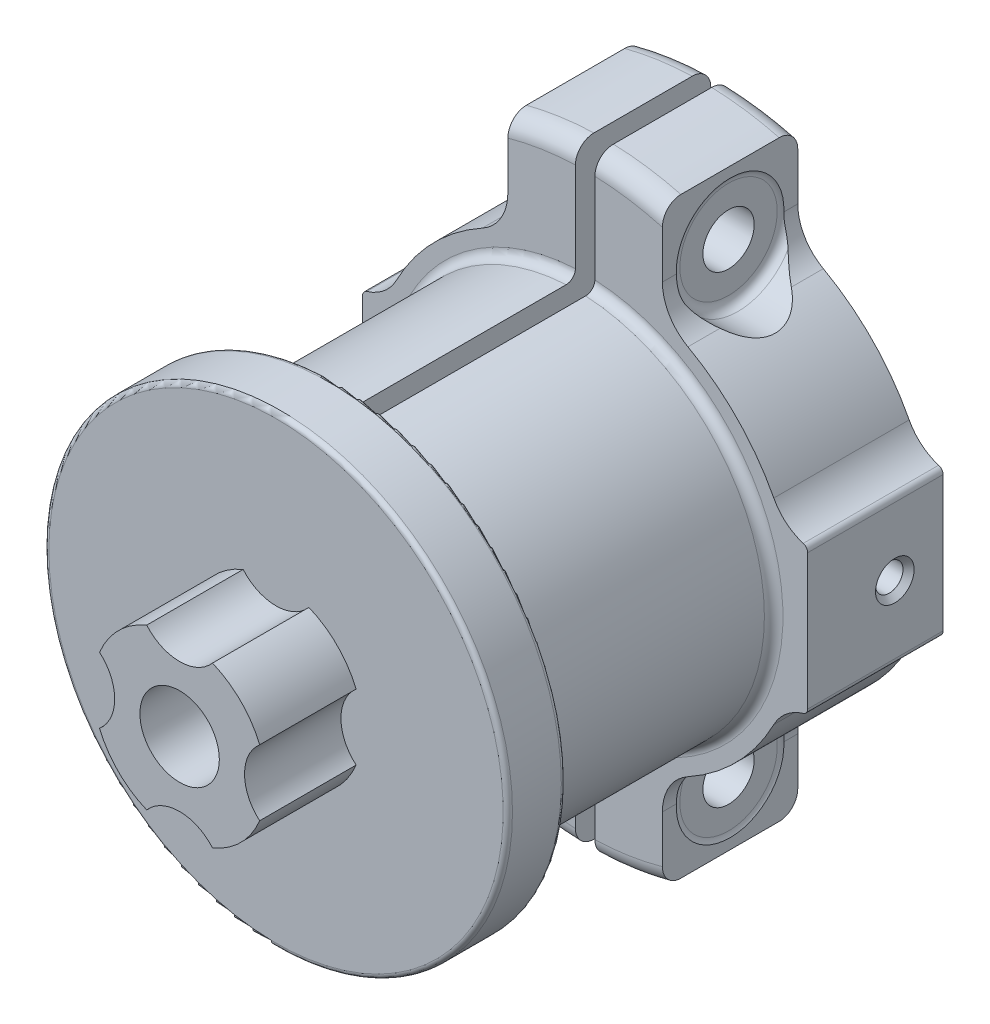
SolidWorks part; units mm, degrees
note: '?' marks a value the reader was unsure of.
ref_plane "front" through (0, 0, 0) normal (0, 0, 1) x (1, 0, 0)
ref_plane "top" through (0, 0, 0) normal (0, 1, 0) x (1, 0, 0)
ref_plane "right" through (0, 0, 0) normal (1, 0, 0) x (0, 0, -1)
ref_axis "Axis1" through (0, 0, -80.9) along (0, 0, 1)?
sketch "Sketch1" plane through (0, 0, 0) normal (1, 0, 0) x (0, 0, -1)
  line L0 (20.6502, 12.7) -> (36.5252, 12.7)
  line L1 (36.5252, 12.7) -> (36.5252, 25.146)
  line L2 (36.5252, 25.146) -> (25.4, 25.146)
  line L3 (25.4, 25.146) -> (25.4, 15.494)
  line L4 (25.4, 15.494) -> (4.7752, 15.494)
  line L5 (4.7752, 15.494) -> (4.7752, 19.05)
  line L6 (4.7752, 19.05) -> (0, 19.05)
  line L7 (0, 19.05) -> (0, 7.112)
  line L8 (22.9625, 0) -> (57.8806, 0) construction
  line L9 (3.175, 12.954) -> (17.0178, 12.954)
  line L10 (17.0178, 12.954) -> (20.6502, 12.7)
  line L11 (3.175, 12.954) -> (3.175, 5.715)
  line L12 (1.7599, 3.2639) -> (-7.9248, 3.2639)
  line L13 (-7.9248, 3.2639) -> (-7.9248, 7.112)
  line L14 (-7.9248, 7.112) -> (0, 7.112)
  line L15 (3.175, 5.715) -> (1.7599, 3.2639)
  dimension "D1" = 50.292
  dimension "D2" = 25.4
  dimension "D3" = 30.988
  dimension "D4" = 38.1
  dimension "D5" = 4.7752
  dimension "D6" = 11.1252
  dimension "D7" = 36.5252
  dimension "D8" = 25.908
  dimension "D9" = 15.875
  dimension "D10" = 4
  dimension "D11" = 6.5278
  dimension "D12" = 14.224
  dimension "D13" = 7.9248
  dimension "D14" = 33.3502
  dimension "D15" = 60
  dimension "D16" = 11.43
revolve "Revolve1" add sketch "Sketch1" angle 360 about L8
fillet "Fillet1" radius 0.762 2 edges at (15.494, 0, -25.4) (15.494, 0, -4.7752)
fillet "Fillet2" radius 1.524 2 edges at (25.146, 0, -36.5252) (25.146, 0, -25.4)
fillet "Fillet3" radius 0.381 2 edges at (19.05, 0, 0) (19.05, 0, -4.7752)
hole_wizard "#8-32 Tapped Hole2" positions "Sketch3" profile "Sketch2" tap size "#8-32" standard "Ansi Inch"
sketch "Sketch3" plane through (0, 0, 0) normal (0, 0, 1) x (1, 0, 0)
  circle A0 centre (0, 0) radius 15.494 construction
  circle A1 centre (12.7, 12.7) radius 2.1082 construction
  point P0 (12.7, 12.7)
  point P3 (-12.7, 12.7)
  point P5 (-12.7, -12.7)
  point P7 (12.7, -12.7)
  dimension "D5" = 4.2164
  dimension "D6" = 30.988
  dimension "D1" = 12.7
  dimension "D2" = 12.7
  dimension "D3" = 12.7
  dimension "D4" = 12.7
sketch "Sketch2" plane through (12.7, 12.7, 0) normal (1, 0, 0) x (0, -1, 0)
  line L0 (0, 0) -> (0, 13.3314)
  line L1 (0, 13.3314) -> (1.7272, 12.2936)
  line L2 (1.7272, 12.2936) -> (1.7272, 0.4572)
  line L3 (1.7272, 0.4572) -> (2.1844, 0)
  line L5 (2.1844, 0) -> (0, 0)
  line L6 (-1.7272, 0.4572) -> (-2.1844, 0) construction
  line L10 (0, 13.3314) -> (-1.7272, 12.2936) construction
  line L11 (0, -6.35) -> (0, 107.95) construction
  dimension "Tap Drill Dia." = 3.4544
  dimension "Tap Drill Depth" = 12.2936
  dimension "Near C'Sink Dia." = 4.3688
  dimension "Near C'Sink Angle" = 90
  dimension "Drill Angle" = 118
sketch "Sketch4" plane through (0, 0, -36.5252) normal (0, 0, -1) x (-1, 0, 0)
  line L0 (6.35, 29.8112) -> (6.35, 18.8543)
  line L1 (6.35, -29.8112) -> (6.35, -18.8543)
  line L2 (4.924, 0) -> (11.1622, 0) construction
  line L3 (18.288, 5.5626) -> (18.288, -5.5626)
  arc A0 (8.4491, 15.2969) -> (15.5044, 8.062) centre (0, 0) cw
  arc A1 (8.4491, -15.2969) -> (15.5044, -8.062) centre (0, 0) ccw
  arc A2 (6.35, -29.8112) -> (6.35, 29.8112) centre (0, 0) ccw
  arc A3 (6.35, 18.8543) -> (8.4491, 15.2969) centre (10.414, 18.8543) ccw
  arc A4 (6.35, -18.8543) -> (8.4491, -15.2969) centre (10.414, -18.8543) cw
  arc A5 (17.9278, 6.0486) -> (15.5044, 8.062) centre (19.1101, 9.9368) cw
  arc A6 (17.9278, 6.0486) -> (18.288, 5.5626) centre (17.78, 5.5626) cw
  arc A7 (17.9278, -6.0486) -> (18.288, -5.5626) centre (17.78, -5.5626) ccw
  arc A8 (17.9278, -6.0486) -> (15.5044, -8.062) centre (19.1101, -9.9368) ccw
  point P18 (15.5044, 8.062)
  dimension "D1" = 4.064
  dimension "D2" = 17.4752
  dimension "D3" = 30.48
  dimension "D6" = 0.508
  dimension "D4" = 6.35
  dimension "D5" = 18.288
  dimension "D9" = 11.1252
extrude "Extrude1" cut sketch "Sketch4" against normal up to next
mirror "Mirror1" about plane through (0, 0, 0) normal (1, 0, 0) of "Extrude1"
sketch "Sketch10" plane through (0, 0, 0) normal (0, 0, 1) x (1, 0, 0)
  line L1 (-17.4625, 17.4625) -> (17.4625, 17.4625)
  line L2 (-17.4625, 17.4625) -> (-17.4625, -17.4625)
  line L3 (-17.4625, -17.4625) -> (17.4625, -17.4625)
  line L4 (17.4625, 17.4625) -> (17.4625, -17.4625)
  point P4 (17.4625, 0)
  point P5 (0, 17.4625)
  dimension "D1" = 34.925
extrude "Extrude4" [suppressed] cut sketch "Sketch10" against normal blind 20.32 flip side to cut
ref_plane "Plane1" through (0, 0, -30.9626) normal (0, 0, -1) x (-1, 0, 0)
sketch "Sketch11" plane through (0, 0, -30.9626) normal (0, 0, -1) x (-1, 0, 0)
  line L0 (-11.303, 23.8125) -> (-6.985, 23.8125)
  line L1 (-6.223, 23.0505) -> (-6.223, 21.1582)
  line L2 (-6.223, 21.1582) -> (0, 21.1582)
  line L3 (0, 21.1582) -> (0, 20.7772)
  line L4 (0, 20.7772) -> (11.43, 20.7772)
  line L5 (11.43, 20.7772) -> (11.43, 19.05)
  line L6 (11.43, 19.05) -> (-11.303, 19.05)
  line L7 (-11.303, 19.05) -> (-11.303, 23.8125)
  line L8 (-11.303, 19.05) -> (-18.4305, 19.05) construction
  line L9 (-6.35, 22.7525) -> (-6.35, 18.8543) construction
  line L10 (6.35, 22.7525) -> (6.35, 18.8543) construction
  arc A0 (-6.985, 23.8125) -> (-6.223, 23.0505) centre (-6.985, 23.0505) cw
  dimension "D4" = 0.762
  dimension "D1" = 3.4544
  dimension "D2" = 4.2164
  dimension "D3" = 9.525
  dimension "D5" = 0.127
  dimension "D6" = 5.08
  dimension "D7" = 19.05
  dimension "D8" = 5.08
revolve "Cut-Revolve1" cut sketch "Sketch11" angle 360 about L8
mirror "Mirror2" about plane through (0, 0, 0) normal (0, 1, 0) of "Cut-Revolve1"
sketch "Sketch5" plane through (0, 0, -36.5252) normal (0, -1, 0) x (-1, 0, 0)
  line L1 (-0.8001, 26.7691) -> (0.8001, 26.7691)
  line L2 (-0.8001, 26.7691) -> (-0.8001, -31.242)
  line L3 (-0.8001, -31.242) -> (0.8001, -31.242)
  line L4 (0.8001, 26.7691) -> (0.8001, -31.242)
  point P4 (0, 26.7691)
  dimension "D1" = 1.6002
  dimension "D2" = 31.242
extrude "Extrude2" cut sketch "Sketch5" against normal mid plane 66.04
hole_wizard "#4-40 Tapped Hole1" positions "Sketch13" profile "Sketch12" tap size "#4-40" standard "Ansi Inch"
sketch "Sketch13" plane through (18.288, 0, 0) normal (1, 0, 0) x (0, 0, -1)
  point P0 (32.5628, 0)
  dimension "D1" = 32.5628
sketch "Sketch12" plane through (18.288, 0, -32.5628) normal (0, 1, 0) x (0, 0, -1)
  line L0 (0, 0) -> (0, 9.5438)
  line L1 (0, 9.5438) -> (1.1303, 8.8646)
  line L2 (1.1303, 8.8646) -> (1.1303, 0.4572)
  line L3 (1.1303, 0.4572) -> (1.5875, 0)
  line L5 (1.5875, 0) -> (0, 0)
  line L6 (-1.1303, 0.4572) -> (-1.5875, 0) construction
  line L10 (0, 9.5438) -> (-1.1303, 8.8646) construction
  line L11 (0, -6.35) -> (0, 107.95) construction
  dimension "Tap Drill Dia." = 2.2606
  dimension "Tap Drill Depth" = 8.8646
  dimension "Near C'Sink Dia." = 3.175
  dimension "Near C'Sink Angle" = 90
  dimension "Drill Angle" = 118
sketch "Sketch14" plane through (0, 0, -36.5252) normal (0, 0, -1) x (-1, 0, 0)
  circle A0 centre (0, 0) radius 15.494
  dimension "D1" = 30.988
sketch "Sketch15" plane through (0, 0, 0) normal (0, 0, 1) x (1, 0, 0)
  circle A0 centre (8.89, 0) radius 3.556
  dimension "D1" = 7.112
  dimension "D2" = 8.89
extrude "Cut-Extrude1" cut sketch "Sketch15" along normal through all
pattern_circular "CirPattern1" count 4 over 360 about axis through (0, 0, 0) along (0, 0, 1) of "Cut-Extrude1"
sketch "Sketch16" plane through (0, 0, 7.9248) normal (0, 0, 1) x (1, 0, 0)
  circle A0 centre (0, 8.509) radius 3.175
  circle A1 centre (8.509, 0) radius 3.175
  circle A2 centre (0, -8.509) radius 3.175
  circle A3 centre (-8.509, 0) radius 3.175
  arc A8 (-2.7023, 6.5786) -> (2.7023, 6.5786) centre (0, 8.89) ccw construction
  arc A9 (-6.5786, -2.7023) -> (-6.5786, 2.7023) centre (-8.89, 0) ccw construction
  arc A10 (6.5786, 2.7023) -> (6.5786, -2.7023) centre (8.89, 0) ccw construction
  arc A11 (2.7023, -6.5786) -> (-2.7023, -6.5786) centre (0, -8.89) ccw construction
  dimension "D1" = 6.35
